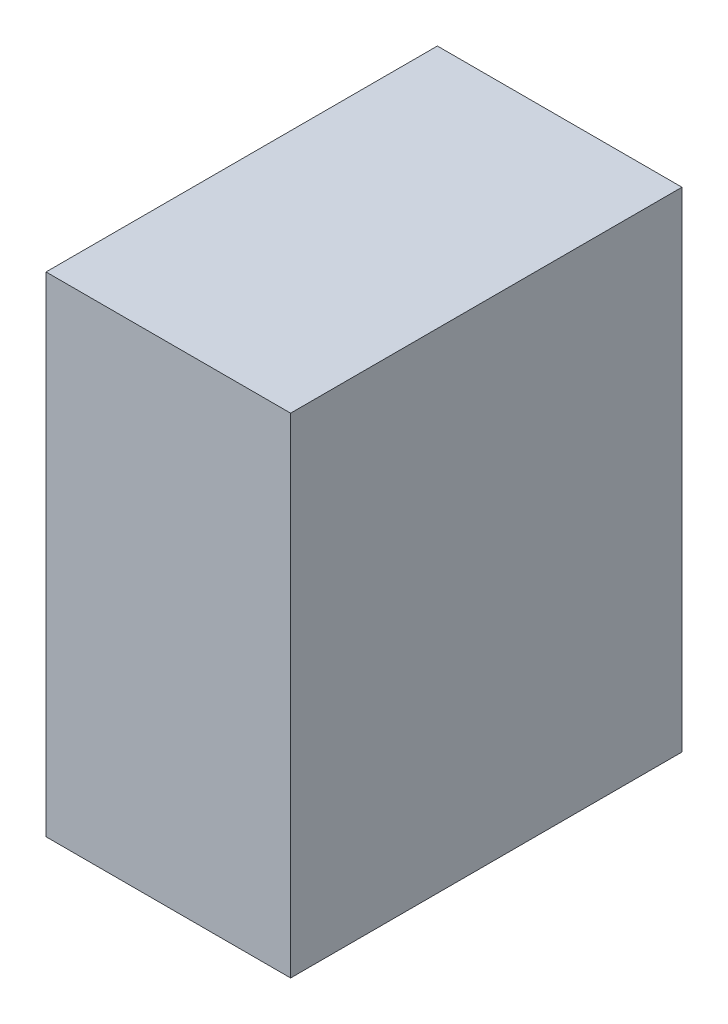
SolidWorks part; units mm, degrees
ref_plane "Front Plane" through (0, 0, 0) normal (0, 0, 1) x (1, 0, 0)
ref_plane "Top Plane" through (0, 0, 0) normal (0, 1, 0) x (1, 0, 0)
ref_plane "Right Plane" through (0, 0, 0) normal (1, 0, 0) x (0, 0, -1)
sketch "Sketch1" plane through (0, 0, 0) normal (0, 0, 1) x (1, 0, 0)
  line L1 (0, 0) -> (0.25, 0)
  line L2 (0, 0) -> (0, 0.5)
  line L3 (0, 0.5) -> (0.25, 0.5)
  line L4 (0.25, 0) -> (0.25, 0.5)
  dimension "D1" = 0.25
  dimension "D2" = 0.5
extrude "Boss-Extrude1" add sketch "Sketch1" along normal blind 0.4 contours L2 L3 L4 L1
equation "\"t\"= 0.25'thickness of the sheets"
equation "\"t_cf\"= 0.115'thickness of single carbon fiber layer"
equation "\"t_kapton\"= 0.025'thickness of single Kapton flex layer"
equation "\"t_fr4\"= 0.1'thickness of FR4 with copper layer"
equation "\"joint_flex\"= 0.1'Width of flextures gap"
equation "\"joint_flex_eff\"= 0.02'Width of flecture after castelation"
equation "\"joint_fold\"= 0.2'Width of folding joints for 90deg fold"
equation "\"gap_tolerance\"= 0.002'Width to have interfecence fit between carbon fiber inserts"
equation "\"assemble_angle\"= 90'Angle of assembly parts"
equation "\"link_lift\"= 0.5'Actuation linkage amplification for the lift motion"
equation "\"link_swing\"= 0.45'Actuation linkage amplification for the swing motion"
equation "\"D1@Sketch1\"=\"t\""
equation "\"D1@Boss-Extrude1\"=\"joint_fold\"*2"
